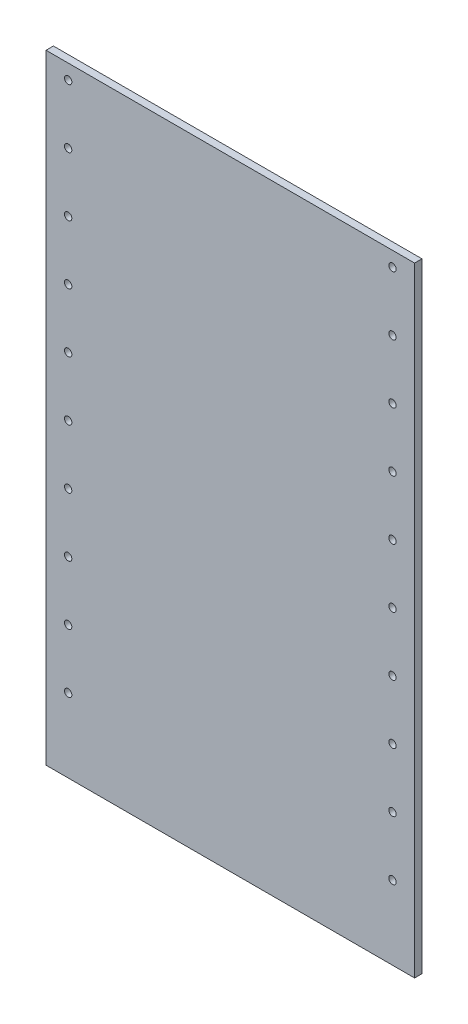
SolidWorks part; units mm, degrees
material "Copper"
ref_plane "Front Plane" through (0, 0, 0) normal (0, 0, 1) x (1, 0, 0)
ref_plane "Top Plane" through (0, 0, 0) normal (0, 1, 0) x (1, 0, 0)
ref_plane "Right Plane" through (0, 0, 0) normal (1, 0, 0) x (0, 0, -1)
sketch "Sketch1" plane through (0, 0, 0) normal (0, 0, 1) x (1, 0, 0)
  line L1 (0, 0) -> (158.76, 0)
  line L2 (0, 0) -> (0, -266.7)
  line L3 (0, -266.7) -> (158.76, -266.7)
  line L4 (158.76, 0) -> (158.76, -266.7)
  circle A0 centre (9.53, -6.35) radius 1.5875
  circle A1 centre (149.23, -6.35) radius 1.5875
  circle A2 centre (149.23, -31.75) radius 1.5875
  circle A3 centre (149.23, -57.15) radius 1.5875
  circle A4 centre (149.23, -82.55) radius 1.5875
  circle A5 centre (149.23, -107.95) radius 1.5875
  circle A6 centre (149.23, -133.35) radius 1.5875
  circle A7 centre (149.23, -158.75) radius 1.5875
  circle A8 centre (149.23, -184.15) radius 1.5875
  circle A9 centre (149.23, -209.55) radius 1.5875
  circle A10 centre (149.23, -234.95) radius 1.5875
  circle A11 centre (9.53, -31.75) radius 1.5875
  circle A12 centre (9.53, -57.15) radius 1.5875
  circle A13 centre (9.53, -82.55) radius 1.5875
  circle A14 centre (9.53, -107.95) radius 1.5875
  circle A15 centre (9.53, -133.35) radius 1.5875
  circle A16 centre (9.53, -158.75) radius 1.5875
  circle A17 centre (9.53, -184.15) radius 1.5875
  circle A18 centre (9.53, -209.55) radius 1.5875
  circle A19 centre (9.53, -234.95) radius 1.5875
  dimension "D3" = 3.175
  dimension "D1" = 158.76
  dimension "D2" = 266.7
  dimension "D4" = 6.35
  dimension "D5" = 9.53
  dimension "D8" = 25.4
  dimension "D9" = 9.53
  dimension "D6" = 2
  dimension "D7" = 10
extrude "Boss-Extrude1" add sketch "Sketch1" along normal blind 3.175
equation "\"D9@Sketch1\"=\"D5@Sketch1\""
